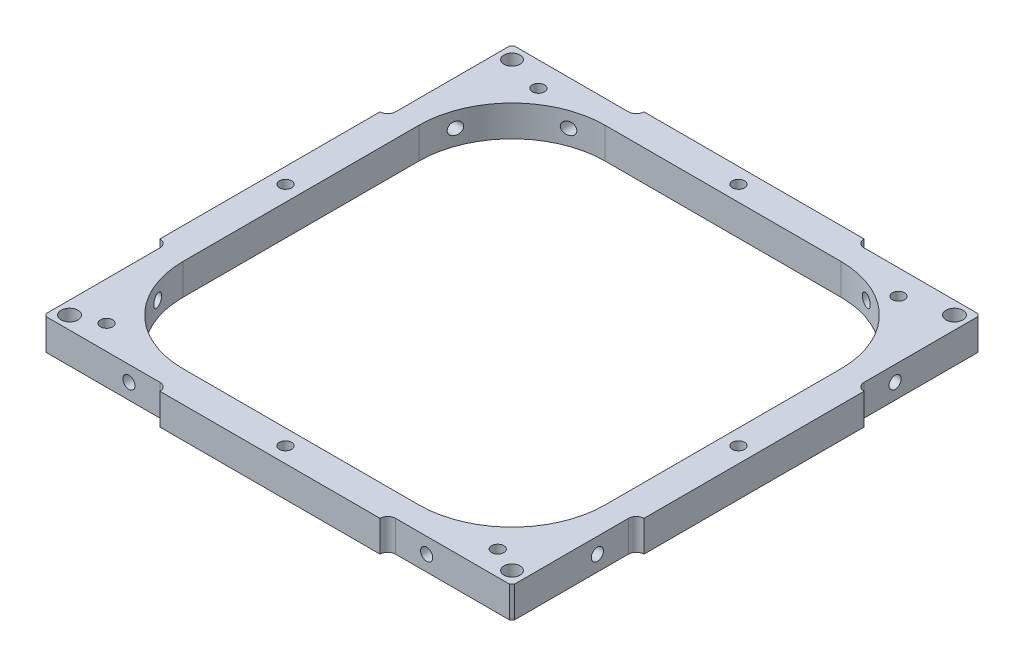
SolidWorks part; units mm, degrees
material "6061-T6 (SS)"
ref_plane "Front Plane" through (0, 0, 0) normal (0, 0, 1) x (1, 0, 0)
ref_plane "Top Plane" through (0, 0, 0) normal (0, 1, 0) x (1, 0, 0)
ref_plane "Right Plane" through (0, 0, 0) normal (1, 0, 0) x (0, 0, -1)
sketch "Sketch1" plane through (0, 0, 0) normal (0, 1, 0) x (1, 0, 0)
  line L0 (-49.5, 22.5125) -> (-47.9125, 22.5125)
  line L1 (-49.5, -49.5) -> (49.5, -49.5)
  line L2 (-49.5, -49.5) -> (-49.5, 49.5)
  line L3 (-49.5, 49.5) -> (49.5, 49.5)
  line L4 (49.5, -49.5) -> (49.5, 49.5)
  line L5 (-49.5, -49.5) -> (49.5, 49.5) construction
  line L6 (-49.5, 49.5) -> (49.5, -49.5) construction
  line L7 (-47.9125, 22.5125) -> (-47.9125, 47.9125)
  line L8 (-47.9125, 47.9125) -> (-22.5125, 47.9125)
  line L9 (-22.5125, 47.9125) -> (-22.5125, 49.5)
  line L10 (22.5125, 49.5) -> (22.5125, 47.9125)
  line L11 (22.5125, 47.9125) -> (47.9125, 47.9125)
  line L12 (47.9125, 47.9125) -> (47.9125, 22.5125)
  line L13 (47.9125, 22.5125) -> (49.5, 22.5125)
  line L14 (49.5, -22.5125) -> (47.9125, -22.5125)
  line L15 (47.9125, -22.5125) -> (47.9125, -47.9125)
  line L16 (47.9125, -47.9125) -> (22.5125, -47.9125)
  line L17 (22.5125, -47.9125) -> (22.5125, -49.5)
  line L18 (-22.5125, -49.5) -> (-22.5125, -47.9125)
  line L19 (-22.5125, -47.9125) -> (-47.9125, -47.9125)
  line L20 (-47.9125, -47.9125) -> (-47.9125, -22.5125)
  line L21 (-47.9125, -22.5125) -> (-49.5, -22.5125)
  point P0 (0, 0)
  dimension "D1" = 99
  dimension "D2" = 99
  dimension "D3" = 26.9875
  dimension "D4" = 1.5875
  dimension "D5" = 26.9875
  dimension "D6" = 1.5875
extrude "Boss-Extrude1" add sketch "Sketch1" along normal blind 6.35 contours L21 L20 L19 L18 L1 L17 L16 L15 L14 L4 L13 L12 L11 L10 L3 L9 L8 L7 L0 L2 region at (0, 0, 0)
chamfer "Chamfer1" distance 0.508 angle 45 4 edges at (47.9125, 3.175, -47.9125) (-47.9125, 3.175, -47.9125) (-47.9125, 3.175, 47.9125) (47.9125, 3.175, 47.9125)
fillet "Fillet1" radius 1.5875 8 edges at (-47.9125, 3.175, -22.5125) (-22.5125, 3.175, -47.9125) (22.5125, 3.175, -47.9125) (47.9125, 3.175, -22.5125) (47.9125, 3.175, 22.5125) (22.5125, 3.175, 47.9125) (-22.5125, 3.175, 47.9125) (-47.9125, 3.175, 22.5125)
hole_wizard "#8-36 Tapped Hole2" positions "Sketch2" profile "Sketch3" tap size "#8-36" standard "ANSI Inch" end condition through all
sketch "Sketch2" plane through (0, 0, 0) normal (0, -1, 0) x (-1, 0, 0)
  line L0 (-49.5, -22.5125) -> (-49.5, 22.5125) construction
  line L1 (22.5125, 49.5) -> (-22.5125, 49.5) construction
  line L5 (49.5, -22.5125) -> (49.5, 22.5125) construction
  line L6 (22.5125, -49.5) -> (-22.5125, -49.5) construction
  point P0 (-45.25, 45.25)
  point P4 (45.25, -45.25)
  dimension "D1" = 4.25
  dimension "D2" = 4.25
  dimension "D5" = 4.25
  dimension "D6" = 4.25
sketch "Sketch3" plane through (45.25, 0, -45.25) normal (1, 0, 0) x (0, 0, -1)
  line L0 (0, 0) -> (0, 6.35)
  line L1 (0, 6.35) -> (1.7272, 6.35)
  line L2 (1.7272, 6.35) -> (1.7272, 0)
  line L5 (1.7272, 0) -> (0, 0)
  line L11 (0, -6.35) -> (0, 107.95) construction
  dimension "Thru Tap Drill Dia." = 3.4544
  dimension "Thru Tap Drill Depth" = 6.35
cosmetic thread "Hole Thread8" parameters "D2"=4.1656
cosmetic thread "Hole Thread9" parameters "D2"=4.1656
hole_wizard "M3x0.5 Tapped Hole1" positions "Sketch6" profile "Sketch7" tap size "M3x0.5" standard "ANSI Metric"
sketch "Sketch6" plane through (0, 0, 47.9125) normal (0, 0, 1) x (1, 0, 0)
  line L1 (-24.1, 0) -> (-47.4045, 0) construction
  line L4 (47.4045, 0) -> (24.1, 0) construction
  line L5 (-24.1, 0) -> (-24.1, 6.35) construction
  line L7 (24.1, 6.35) -> (24.1, 0) construction
  point P0 (-30.45, 3.175)
  point P2 (30.45, 3.175)
  dimension "D1" = 6.35
  dimension "D2" = 3.175
  dimension "D3" = 6.35
  dimension "D4" = 3.175
sketch "Sketch7" plane through (-30.45, 3.175, 47.9125) normal (1, 0, 0) x (0, -1, 0)
  line L0 (0, 0) -> (0, 8.3711)
  line L1 (0, 8.3711) -> (1.25, 7.62)
  line L2 (1.25, 7.62) -> (1.25, 0)
  line L5 (1.25, 0) -> (0, 0)
  line L10 (0, 8.3711) -> (-1.25, 7.62) construction
  line L11 (0, -6.35) -> (0, 107.95) construction
  dimension "Tap Drill Dia." = 2.5
  dimension "Tap Drill Depth" = 7.62
  dimension "Drill Angle" = 118
cosmetic thread "Hole Thread1" parameters "D1"=4.7625, "D2"=3
cosmetic thread "Hole Thread2" parameters "D1"=4.7625, "D2"=3
ref_plane "Plane1" through (0, 0, 0) normal (0, 0, 1) x (1, 0, 0)
ref_plane "Plane2" through (0, 0, 0) normal (-1, 0, 0) x (0, 0, 1)
ref_axis "Axis1" through (0, -0.3175, 0) along (0, 1, 0)
pattern_circular "CirPattern1" count 4 over 360 about axis through (0, -0.3175, 0) along (0, 1, 0) of "M3x0.5 Tapped Hole1"
sketch "Sketch9" plane through (0, 6.35, 0) normal (0, 1, 0) x (1, 0, 0)
  line L0 (0, 3.4925) -> (0, -3.4925) construction
  line L1 (-3.4925, 0) -> (3.4925, 0) construction
  circle A0 centre (-40.005, -42.926) radius 0.7937
  circle A1 centre (40.005, -42.926) radius 0.7937
  circle A2 centre (36.195, 42.8625) radius 0.7937
  circle A3 centre (-37.465, 42.8625) radius 0.7937
  dimension "D7" = 1.5875
  dimension "D1" = 40.005
  dimension "D2" = 40.005
  dimension "D3" = 2.54
  dimension "D4" = 73.66
  dimension "D5" = 42.8625
  dimension "D6" = 42.926
extrude "Cut-Extrude2" cut sketch "Sketch9" against normal through all
sketch "Sketch11" plane through (0, 6.35, 0) normal (0, 1, 0) x (1, 0, 0)
  line L0 (-22.5125, 49.5) -> (22.5125, 49.5) construction
  line L1 (-43.15, -43.15) -> (43.15, -43.15)
  line L2 (-43.15, -43.15) -> (-43.15, 43.15)
  line L3 (-43.15, 43.15) -> (43.15, 43.15)
  line L4 (43.15, -43.15) -> (43.15, 43.15)
  line L5 (-43.15, -43.15) -> (43.15, 43.15) construction
  line L6 (-43.15, 43.15) -> (43.15, -43.15) construction
  line L7 (49.5, -22.5125) -> (49.5, 22.5125) construction
  line L8 (-44.2725, 42.0275) -> (42.0275, -44.2725)
  line L9 (-42.0275, -44.2725) -> (44.2725, 42.0275)
  line L10 (-42.0275, 44.2725) -> (44.2725, -42.0275)
  line L11 (-44.2725, -42.0275) -> (42.0275, 44.2725)
  circle A5 centre (-37.465, 42.8625) radius 3.9687
  circle A6 centre (-37.465, 42.8625) radius 3.9687
  circle A9 centre (36.195, 42.8625) radius 3.9687
  circle A10 centre (36.195, 42.8625) radius 3.9687
  circle A12 centre (-40.005, -42.926) radius 3.9688
  circle A13 centre (-40.005, -42.926) radius 3.9687
  circle A14 centre (0, 0) radius 25.4
  circle A15 centre (40.005, -42.926) radius 3.9688
  circle A16 centre (40.005, -42.926) radius 3.9687
  circle A17 centre (0, 0) radius 22.225
  point P0 (0, 0)
  dimension "D9" = 50.8
  dimension "D1" = 6.35
  dimension "D2" = 6.35
  dimension "D3" = 3.175
  dimension "D4" = 3.175
  dimension "D5" = 3.175
  dimension "D6" = 3.175
  dimension "D7" = 1.5875
  dimension "D8" = 1.5875
  dimension "D10" = 3.175
hole_wizard "M3x0.5 Tapped Hole3" positions "Sketch14" profile "Sketch15" tap size "M3x0.5" standard "ANSI Metric"
sketch "Sketch14" plane through (0, 6.35, 0) normal (0, 1, 0) x (1, 0, 0)
  line L0 (0, 3.4925) -> (0, -3.4925) construction
  line L1 (-22.5125, -49.5) -> (22.5125, -49.5) construction
  point P0 (0, -46.325)
  dimension "D1" = 3.175
sketch "Sketch15" plane through (0, 6.35, 46.325) normal (1, 0, 0) x (0, 0, 1)
  line L0 (0, 0) -> (0, 8.3711)
  line L1 (0, 8.3711) -> (1.25, 7.62)
  line L2 (1.25, 7.62) -> (1.25, 0)
  line L5 (1.25, 0) -> (0, 0)
  line L10 (0, 8.3711) -> (-1.25, 7.62) construction
  line L11 (0, -6.35) -> (0, 107.95) construction
  dimension "Tap Drill Dia." = 2.5
  dimension "Tap Drill Depth" = 7.62
  dimension "Drill Angle" = 118
cosmetic thread "Hole Thread5" parameters "D1"=6.096, "D2"=3
sketch "Sketch16" plane through (0, 6.35, 0) normal (0, 1, 0) x (1, 0, 0)
  line L0 (-22.5125, 49.5) -> (22.5125, 49.5) construction
  line L1 (-43.15, -43.15) -> (43.15, -43.15)
  line L2 (-43.15, -43.15) -> (-43.15, 43.15)
  line L3 (-43.15, 43.15) -> (43.15, 43.15)
  line L4 (43.15, -43.15) -> (43.15, 43.15)
  line L5 (-43.15, -43.15) -> (43.15, 43.15) construction
  line L6 (-43.15, 43.15) -> (43.15, -43.15) construction
  line L7 (49.5, -22.5125) -> (49.5, 22.5125) construction
  arc A0 (24.1, 43.15) -> (43.15, 24.1) centre (24.1, 24.1) cw
  arc A1 (43.15, -24.1) -> (24.1, -43.15) centre (24.1, -24.1) cw
  arc A2 (-24.1, -43.15) -> (-43.15, -24.1) centre (-24.1, -24.1) cw
  arc A3 (-43.15, 24.1) -> (-24.1, 43.15) centre (-24.1, 24.1) cw
  circle A4 centre (36.195, 42.8625) radius 3.2731 construction
  circle A5 centre (36.195, 42.8625) radius 0.7937 construction
  point P0 (0, 0)
  dimension "D3" = 19.05
  dimension "D1" = 6.35
  dimension "D2" = 6.35
extrude "Cut-Extrude3" cut sketch "Sketch16" against normal through all contours A3 L2 A2 L1 A1 L4 A0 L3 region at (0, 6.35, 0)
pattern_circular "CirPattern2" count 4 over 360 about axis through (0, -0.3175, 0) along (0, 1, 0) of "M3x0.5 Tapped Hole3"
sketch "Sketch17" plane through (0, 6.35, 0) normal (0, 1, 0) x (1, 0, 0)
  circle A0 centre (-37.465, 42.8625) radius 3.25
  circle A1 centre (36.195, 42.8625) radius 3.25
  circle A2 centre (40.005, -42.926) radius 3.25
  circle A3 centre (-40.005, -42.926) radius 3.25
  dimension "D1" = 6.5
  dimension "D2" = 6.5
  dimension "D3" = 6.5
  dimension "D4" = 6.5
hole_wizard "M4x0.7 Tapped Hole1" positions "Sketch18" profile "Sketch19" tap size "M4x0.7" standard "ANSI Metric" end condition through all
sketch "Sketch18" plane through (0, 6.35, 0) normal (0, 1, 0) x (1, 0, 0)
  line L0 (-22.5125, 49.5) -> (22.5125, 49.5) construction
  line L1 (-49.5, -22.5125) -> (-49.5, 22.5125) construction
  line L2 (-22.5125, -49.5) -> (22.5125, -49.5) construction
  line L3 (49.5, -22.5125) -> (49.5, 22.5125) construction
  point P0 (-45.25, 45.25)
  point P2 (45.25, -45.25)
  dimension "D1" = 4.25
  dimension "D2" = 4.25
  dimension "D3" = 4.25
  dimension "D4" = 4.25
sketch "Sketch19" plane through (-45.25, 6.35, -45.25) normal (1, 0, 0) x (0, 0, 1)
  line L0 (0, 0) -> (0, 6.35)
  line L1 (0, 6.35) -> (1.65, 6.35)
  line L2 (1.65, 6.35) -> (1.65, 0)
  line L5 (1.65, 0) -> (0, 0)
  line L11 (0, -6.35) -> (0, 107.95) construction
  dimension "Thru Tap Drill Dia." = 3.3
  dimension "Thru Tap Drill Depth" = 6.35
cosmetic thread "Hole Thread6" parameters "D2"=4
cosmetic thread "Hole Thread7" parameters "D2"=4
hole_wizard "M3x0.5 Tapped Hole4" positions "Sketch20" profile "Sketch21" tap size "M3x0.5" standard "ANSI Metric" end condition through all
sketch "Sketch20" plane through (0, 6.35, 0) normal (0, 1, 0) x (1, 0, 0)
  point P0 (36.195, 42.8625)
  point P3 (-37.465, 42.8625)
  point P6 (-40.005, -42.926)
  point P9 (40.005, -42.926)
sketch "Sketch21" plane through (36.195, 6.35, -42.8625) normal (1, 0, 0) x (0, 0, 1)
  line L0 (0, 0) -> (0, 6.35)
  line L1 (0, 6.35) -> (1.25, 6.35)
  line L2 (1.25, 6.35) -> (1.25, 0)
  line L5 (1.25, 0) -> (0, 0)
  line L11 (0, -6.35) -> (0, 107.95) construction
  dimension "Thru Tap Drill Dia." = 2.5
  dimension "Thru Tap Drill Depth" = 6.35
cosmetic thread "Hole Thread10" parameters "D2"=3
cosmetic thread "Hole Thread11" parameters "D2"=3
cosmetic thread "Hole Thread12" parameters "D2"=3
cosmetic thread "Hole Thread13" parameters "D2"=3
sketch "Sketch22" plane through (0, 6.35, 0) normal (0, 1, 0) x (1, 0, 0)
  line L0 (45.25, 45.25) -> (45.25, 42.25) construction
  line L1 (45.25, 45.25) -> (42.25, 45.25) construction
  circle A0 centre (45.25, 42.25) radius 0.5
  circle A1 centre (42.25, 45.25) radius 0.5
  dimension "D2" = 1
  dimension "D3" = 1
  dimension "D1" = 3
